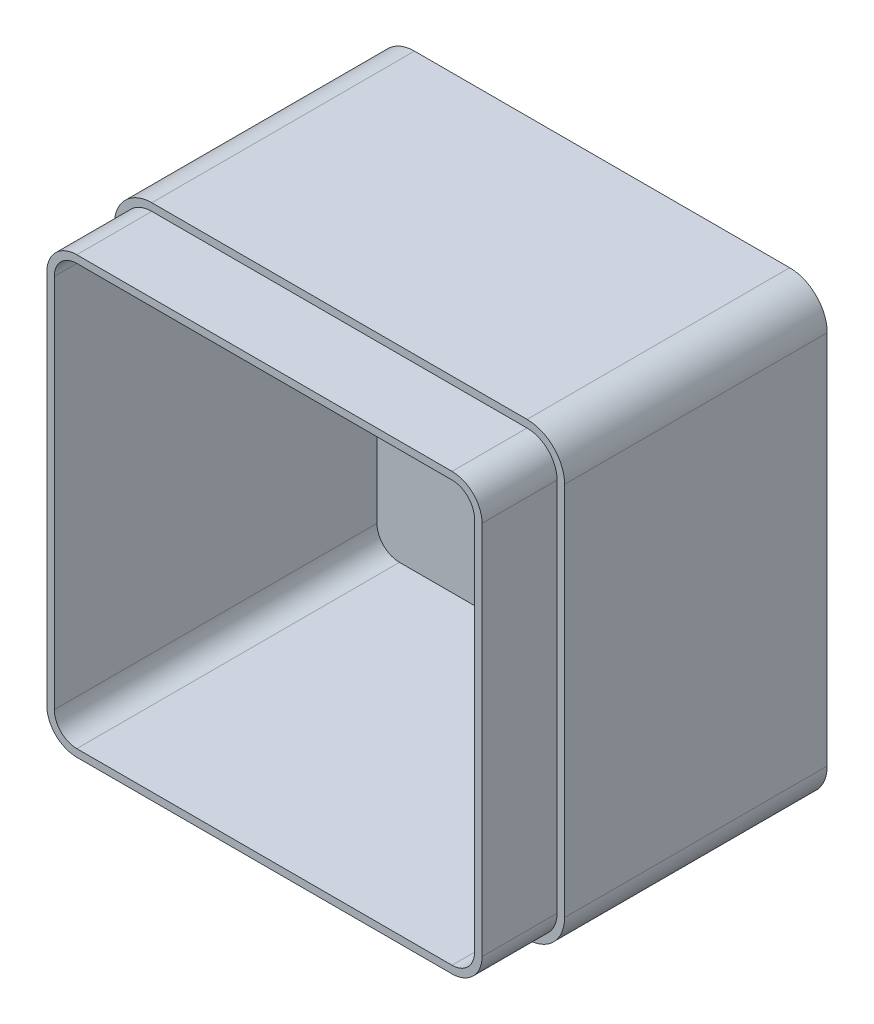
SolidWorks part; units mm, degrees
ref_plane "Front Plane" through (0, 0, 0) normal (0, 0, 1) x (1, 0, 0)
ref_plane "Top Plane" through (0, 0, 0) normal (0, 1, 0) x (1, 0, 0)
ref_plane "Right Plane" through (0, 0, 0) normal (1, 0, 0) x (0, 0, -1)
sketch "Sketch1" plane through (0, 0, 0) normal (0, 0, 1) x (1, 0, 0)
  line L1 (-39.9038, 25.9719) -> (80.0962, 25.9719)
  line L2 (-39.9038, 25.9719) -> (-39.9038, -94.0281)
  line L3 (-39.9038, -94.0281) -> (80.0962, -94.0281)
  line L4 (80.0962, 25.9719) -> (80.0962, -94.0281)
  dimension "D1" = 120
  dimension "D2" = 120
extrude "Boss-Extrude1" add sketch "Sketch1" along normal blind 90
fillet "Fillet1" radius 10 4 edges at (-39.9038, -94.0281, 45) (80.0962, -94.0281, 45) (-39.9038, 25.9719, 45) (80.0962, 25.9719, 45)
shell "Shell1" thickness 4 removed face at (20.0962, -34.0281, 90)
sketch "Sketch3" plane through (0, 0, 90) normal (0, 0, 1) x (1, 0, 0)
  line L4 (-39.9038, 15.9719) -> (-39.9038, -84.0281)
  line L5 (-29.9038, -94.0281) -> (70.0962, -94.0281)
  line L6 (80.0962, -84.0281) -> (80.0962, 15.9719)
  line L7 (70.0962, 25.9719) -> (-29.9038, 25.9719)
  line L8 (-39.9038, 15.9719) -> (-39.9038, -84.0281)
  line L9 (-29.9038, -94.0281) -> (70.0962, -94.0281)
  line L10 (80.0962, -84.0281) -> (80.0962, 15.9719)
  line L11 (70.0962, 25.9719) -> (-29.9038, 25.9719)
  line L16 (-37.9038, 15.9719) -> (-37.9038, -84.0281)
  line L17 (-29.9038, -92.0281) -> (70.0962, -92.0281)
  line L18 (78.0962, -84.0281) -> (78.0962, 15.9719)
  line L19 (70.0962, 23.9719) -> (-29.9038, 23.9719)
  line L20 (-37.9038, 15.9719) -> (-37.9038, -84.0281)
  line L21 (-29.9038, -92.0281) -> (70.0962, -92.0281)
  line L22 (78.0962, -84.0281) -> (78.0962, 15.9719)
  line L23 (70.0962, 23.9719) -> (-29.9038, 23.9719)
  arc A4 (-39.9038, -84.0281) -> (-29.9038, -94.0281) centre (-29.9038, -84.0281) ccw
  arc A5 (70.0962, -94.0281) -> (80.0962, -84.0281) centre (70.0962, -84.0281) ccw
  arc A6 (80.0962, 15.9719) -> (70.0962, 25.9719) centre (70.0962, 15.9719) ccw
  arc A7 (-29.9038, 25.9719) -> (-39.9038, 15.9719) centre (-29.9038, 15.9719) ccw
  arc A8 (-39.9038, -84.0281) -> (-29.9038, -94.0281) centre (-29.9038, -84.0281) ccw
  arc A9 (70.0962, -94.0281) -> (80.0962, -84.0281) centre (70.0962, -84.0281) ccw
  arc A10 (80.0962, 15.9719) -> (70.0962, 25.9719) centre (70.0962, 15.9719) ccw
  arc A11 (-29.9038, 25.9719) -> (-39.9038, 15.9719) centre (-29.9038, 15.9719) ccw
  arc A16 (-37.9038, -84.0281) -> (-29.9038, -92.0281) centre (-29.9038, -84.0281) ccw
  arc A17 (70.0962, -92.0281) -> (78.0962, -84.0281) centre (70.0962, -84.0281) ccw
  arc A18 (78.0962, 15.9719) -> (70.0962, 23.9719) centre (70.0962, 15.9719) ccw
  arc A19 (-29.9038, 23.9719) -> (-37.9038, 15.9719) centre (-29.9038, 15.9719) ccw
  arc A20 (-37.9038, -84.0281) -> (-29.9038, -92.0281) centre (-29.9038, -84.0281) ccw
  arc A21 (70.0962, -92.0281) -> (78.0962, -84.0281) centre (70.0962, -84.0281) ccw
  arc A22 (78.0962, 15.9719) -> (70.0962, 23.9719) centre (70.0962, 15.9719) ccw
  arc A23 (-29.9038, 23.9719) -> (-37.9038, 15.9719) centre (-29.9038, 15.9719) ccw
  dimension "D1" = 0
  dimension "D2" = 2
extrude "Cut-Extrude2" cut sketch "Sketch3" against normal blind 20
